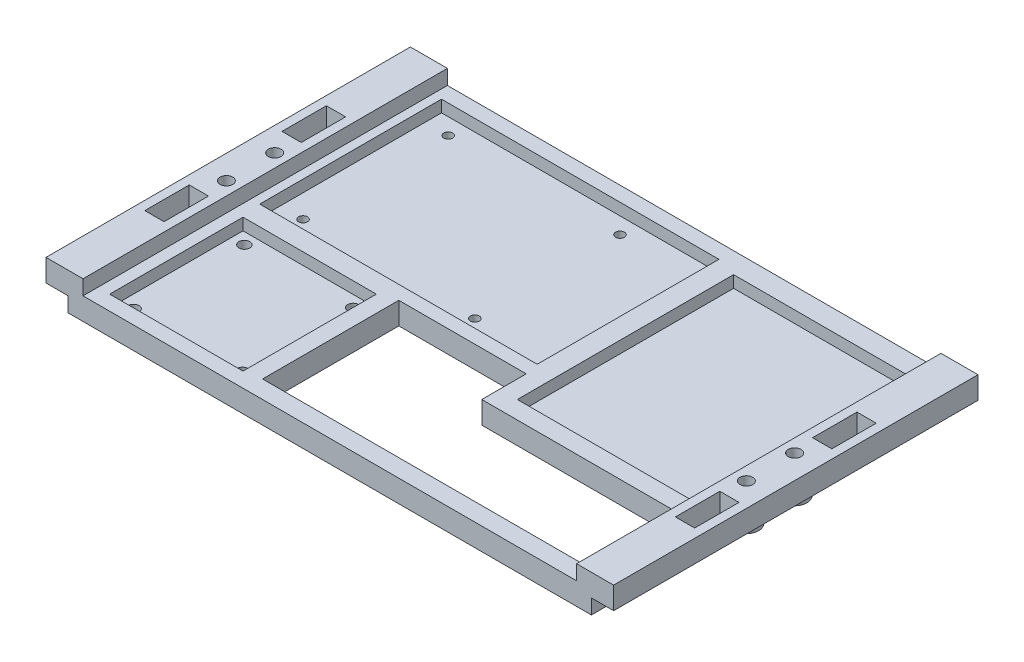
SolidWorks part; units mm, degrees
ref_plane "Front Plane" through (0, 0, 0) normal (0, 0, 1) x (1, 0, 0)
ref_plane "Top Plane" through (0, 0, 0) normal (0, 1, 0) x (1, 0, 0)
ref_plane "Right Plane" through (0, 0, 0) normal (1, 0, 0) x (0, 0, -1)
sketch "Sketch2" plane through (0, 0, 0) normal (0, 0, 1) x (1, 0, 0)
  line L0 (179.1, 12.5) -> (191.6, 12.5)
  line L1 (7.5, 0) -> (184.1, 0)
  line L2 (0, 5) -> (0, 12.5)
  line L3 (0, 12.5) -> (12.5, 12.5)
  line L4 (191.6, 5) -> (191.6, 12.5)
  line L7 (0, 5) -> (7.5, 5)
  line L8 (7.5, 0) -> (7.5, 5)
  line L11 (191.6, 5) -> (184.1, 5)
  line L12 (184.1, 0) -> (184.1, 5)
  line L14 (12.5, 12.5) -> (12.5, 7.5)
  line L15 (12.5, 7.5) -> (179.1, 7.5)
  line L16 (179.1, 12.5) -> (179.1, 7.5)
  dimension "D1" = 191.6
  dimension "D2" = 5
  dimension "D3" = 5
  dimension "D4" = 5
  dimension "D5" = 12.5
  dimension "D6" = 7.5
  dimension "D7" = 7.5
  dimension "D8" = 12.5
  dimension "D9" = 12.5
extrude "PlateFrame" add sketch "Sketch2" along normal blind 150
sketch "Sketch3" plane through (0, 12.5, 0) normal (0, 1, 0) x (1, 0, 0)
  line L0 (12.5, 0) -> (0, 0) construction
  line L2 (0, -150) -> (0, 0) construction
  line L3 (191.6, -150) -> (191.6, 0) construction
  line L4 (191.6, 0) -> (179.1, 0) construction
  circle A0 centre (8.05, -66.85) radius 2.5
  circle A1 centre (8.05, -83.15) radius 2.5
  circle A2 centre (183.55, -66.85) radius 2.5
  circle A3 centre (183.55, -83.15) radius 2.5
  dimension "D1" = 5
  dimension "D2" = 5
  dimension "D3" = 5
  dimension "D4" = 5
  dimension "D5" = 66.85
  dimension "D6" = 16.3
  dimension "D7" = 8.05
  dimension "D8" = 8.05
  dimension "D9" = 8.05
  dimension "D10" = 8.05
  dimension "D11" = 66.85
  dimension "D12" = 16.3
  dimension "D13" = 175.5
extrude "HoleSupport" cut sketch "Sketch3" against normal through all
sketch "Sketch4" plane through (0, 12.5, 0) normal (0, 1, 0) x (1, 0, 0)
  circle A0 centre (8.05, -66.85) radius 2.15
  circle A1 centre (8.05, -83.15) radius 2.15
  circle A2 centre (183.55, -83.15) radius 2.15
  circle A3 centre (183.55, -66.85) radius 2.15
  circle A4 centre (183.55, -66.85) radius 4.15
  circle A5 centre (183.55, -83.15) radius 4.15
  circle A6 centre (8.05, -66.85) radius 4.15
  circle A7 centre (8.05, -83.15) radius 4.15
  dimension "D1" = 2
extrude "CylindricalSupports" add sketch "Sketch4" against normal blind 12.5
sketch "Sketch5" plane through (0, 7.5, 0) normal (0, 1, 0) x (1, 0, 0)
  line L0 (12.5, -150) -> (12.5, 0) construction
  line L1 (17.5, -87) -> (60.5, -87)
  line L2 (12.5, -150) -> (12.5, 0) construction
  line L3 (17.5, -20) -> (107.15, -20)
  line L4 (17.5, -20) -> (17.5, -77.35)
  line L5 (17.5, -77.35) -> (107.15, -77.35)
  line L6 (107.15, -20) -> (107.15, -77.35)
  line L7 (174.1, -20) -> (116.1, -20)
  line L8 (174.1, -20) -> (174.1, -93)
  line L9 (174.1, -93) -> (116.1, -93)
  line L10 (116.1, -20) -> (116.1, -93)
  line L15 (179.1, -150) -> (179.1, 0) construction
  line L16 (179.1, 0) -> (12.5, 0) construction
  line L17 (17.5, -87) -> (17.5, -130)
  line L18 (17.5, -130) -> (60.5, -130)
  line L19 (60.5, -87) -> (60.5, -130)
  line L20 (179.1, -150) -> (12.5, -150) construction
  dimension "D1" = 5
  dimension "D2" = 89.65
  dimension "D3" = 57.35
  dimension "D4" = 5
  dimension "D5" = 43
  dimension "D6" = 58
  dimension "D7" = 43
  dimension "D8" = 20
  dimension "D9" = 20
  dimension "D10" = 5
  dimension "D11" = 73
  dimension "D12" = 20
extrude "ItemLayout" cut sketch "Sketch5" against normal blind 4
sketch "Sketch6" plane through (0, 7.5, 0) normal (0, 1, 0) x (1, 0, 0)
  line L1 (67.1, -84) -> (110.1, -84)
  line L2 (67.1, -84) -> (67.1, -130)
  line L3 (67.1, -130) -> (110.1, -130)
  line L4 (110.1, -84) -> (110.1, -99)
  line L9 (179.1, -150) -> (179.1, 0) construction
  line L10 (110.1, -130) -> (174.1, -130)
  line L12 (110.1, -99) -> (174.1, -99)
  line L13 (174.1, -130) -> (174.1, -99)
  line L14 (116.1, -93) -> (174.1, -93) construction
  line L15 (116.1, -20) -> (116.1, -93) construction
  line L17 (179.1, -150) -> (12.5, -150) construction
  dimension "D1" = 20
  dimension "D2" = 43
  dimension "D3" = 5
  dimension "D4" = 6
  dimension "D5" = 6
  dimension "D6" = 15
extrude "HoleCutout" cut sketch "Sketch6" against normal blind 7.5
sketch "Sketch7" plane through (0, 3.5, 0) normal (0, 1, 0) x (1, 0, 0)
  line L0 (17.5, -20) -> (17.5, -77.35) construction
  line L1 (17.5, -20) -> (17.5, -77.35) construction
  line L2 (107.15, -20) -> (17.5, -20) construction
  line L3 (107.15, -20) -> (17.5, -20) construction
  circle A0 centre (23.26, -23.5) radius 1.5
  circle A1 centre (23.26, -72.5) radius 1.5
  circle A2 centre (81.26, -72.5) radius 1.5
  circle A3 centre (81.26, -23.5) radius 1.5
  dimension "D1" = 3
  dimension "D2" = 3
  dimension "D3" = 3
  dimension "D4" = 3
  dimension "D5" = 5.76
  dimension "D6" = 5.76
  dimension "D7" = 3.5
  dimension "D8" = 3.5
  dimension "D9" = 58
  dimension "D10" = 58
  dimension "D11" = 49
  dimension "D12" = 49
extrude "HoleRaspberryPi" cut sketch "Sketch7" against normal blind 3.5
sketch "Sketch8" plane through (0, 3.5, 0) normal (0, 1, 0) x (1, 0, 0)
  line L0 (17.5, -130) -> (60.5, -130) construction
  line L1 (60.5, -87) -> (17.5, -87) construction
  line L2 (60.5, -130) -> (60.5, -87) construction
  line L3 (60.5, -130) -> (60.5, -87) construction
  line L4 (17.5, -87) -> (17.5, -130) construction
  line L5 (17.5, -130) -> (60.5, -130) construction
  circle A0 centre (57.56, -127.24) radius 1.85
  circle A1 centre (57.56, -89.86) radius 1.85
  circle A2 centre (20.81, -89.86) radius 1.85
  circle A3 centre (20.81, -127.24) radius 1.85
  dimension "D1" = 3.7
  dimension "D2" = 3.7
  dimension "D3" = 3.7
  dimension "D4" = 3.7
  dimension "D6" = 2.86
  dimension "D8" = 2.94
  dimension "D9" = 2.86
  dimension "D10" = 3.31
  dimension "D11" = 2.76
  dimension "D12" = 3.31
  dimension "D5" = 2.76
  dimension "D7" = 2.94
extrude "HoleMotorDriver" cut sketch "Sketch8" against normal blind 3.5
sketch "Sketch10" plane through (0, 7.5, 0) normal (0, 1, 0) x (1, 0, 0)
  line L1 (17.5, -87) -> (60.5, -87)
  line L2 (17.5, -87) -> (17.5, -130)
  line L3 (17.5, -130) -> (60.5, -130)
  line L4 (60.5, -87) -> (60.5, -130)
  line L5 (16.5, -86) -> (61.5, -86)
  line L6 (16.5, -86) -> (16.5, -131)
  line L7 (16.5, -131) -> (61.5, -131)
  line L8 (61.5, -86) -> (61.5, -131)
  dimension "D1" = 1
  dimension "D2" = 1
  dimension "D3" = 1
  dimension "D4" = 1
extrude "CutMotorDriver" cut sketch "Sketch10" against normal blind 4
sketch "Sketch11" plane through (0, 7.5, 0) normal (0, 1, 0) x (1, 0, 0)
  line L1 (17.5, -20) -> (107.15, -20)
  line L2 (17.5, -20) -> (17.5, -77.35)
  line L3 (17.5, -77.35) -> (107.15, -77.35)
  line L4 (107.15, -20) -> (107.15, -77.35)
  line L5 (109.15, -79.35) -> (15.5, -79.35)
  line L6 (109.15, -79.35) -> (109.15, -18)
  line L7 (109.15, -18) -> (15.5, -18)
  line L8 (15.5, -79.35) -> (15.5, -18)
  dimension "D1" = 2
  dimension "D2" = 2
  dimension "D3" = 2
  dimension "D4" = 2
extrude "CutPaspberryPi" cut sketch "Sketch11" against normal blind 4
sketch "Sketch12" plane through (0, 12.5, 0) normal (0, 1, 0) x (1, 0, 0)
  line L0 (191.6, -150) -> (191.6, 0) construction
  line L1 (0, 0) -> (191.6, 0)
  line L2 (0, 0) -> (0, -13)
  line L3 (0, -13) -> (191.6, -13)
  line L4 (191.6, 0) -> (191.6, -13)
  line L6 (0, -150) -> (191.6, -150)
  line L7 (0, -150) -> (0, -136)
  line L8 (0, -136) -> (191.6, -136)
  line L9 (191.6, -150) -> (191.6, -136)
  dimension "D1" = 13
  dimension "D2" = 14
extrude "CutPlateEdges" cut sketch "Sketch12" against normal blind 12.5
sketch "Sketch13" plane through (0, 12.5, 0) normal (0, 1, 0) x (1, 0, 0)
  line L0 (12.5, -136) -> (12.5, -13) construction
  line L1 (9.5, -59.35) -> (3, -59.35)
  line L2 (9.5, -59.35) -> (9.5, -44.35)
  line L3 (9.5, -44.35) -> (3, -44.35)
  line L4 (3, -59.35) -> (3, -44.35)
  line L5 (3, -90.65) -> (9.5, -90.65)
  line L6 (3, -90.65) -> (3, -105.65)
  line L7 (3, -105.65) -> (9.5, -105.65)
  line L8 (9.5, -90.65) -> (9.5, -105.65)
  line L9 (182.1, -59.35) -> (188.6, -59.35)
  line L10 (182.1, -59.35) -> (182.1, -44.35)
  line L11 (182.1, -44.35) -> (188.6, -44.35)
  line L12 (188.6, -59.35) -> (188.6, -44.35)
  line L13 (182.1, -90.65) -> (188.6, -90.65)
  line L14 (182.1, -90.65) -> (182.1, -105.65)
  line L15 (182.1, -105.65) -> (188.6, -105.65)
  line L16 (188.6, -90.65) -> (188.6, -105.65)
  line L18 (179.1, -136) -> (179.1, -13) construction
  line L19 (179.1, -136) -> (179.1, -13) construction
  circle A4 centre (8.05, -66.85) radius 2.15 construction
  circle A5 centre (8.05, -83.15) radius 2.15 construction
  circle A6 centre (183.55, -66.85) radius 2.15 construction
  circle A7 centre (183.55, -83.15) radius 2.15 construction
  dimension "D2" = 7.5
  dimension "D9" = 7.5
  dimension "D10" = 7.5
  dimension "D3" = 3
  dimension "D4" = 6.5
  dimension "D5" = 15
  dimension "D6" = 3
  dimension "D7" = 6.5
  dimension "D8" = 15
  dimension "D11" = 3
  dimension "D12" = 3
  dimension "D13" = 6.5
  dimension "D14" = 6.5
  dimension "D15" = 15
  dimension "D16" = 15
  dimension "D17" = 7.5
extrude "CutShellHoles" cut sketch "Sketch13" against normal blind 12.5
